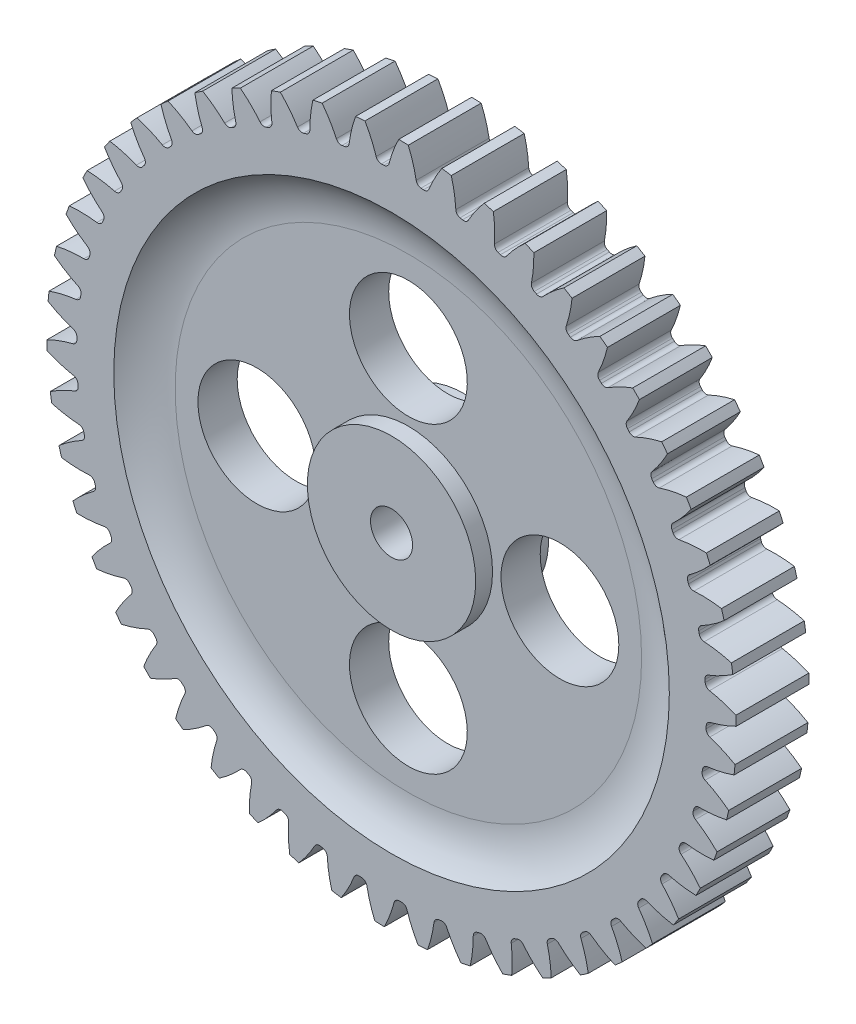
SolidWorks part; units mm, degrees
material "ABS"
ref_plane "Front" through (0, 0, 0) normal (0, 0, 1) x (1, 0, 0)
ref_plane "Top" through (0, 0, 0) normal (0, 1, 0) x (1, 0, 0)
ref_plane "Right" through (0, 0, 0) normal (1, 0, 0) x (0, 0, -1)
sketch "Sketch3" plane through (0, 0, 0) normal (0, 0, 1) x (1, 0, 0)
  circle A0 centre (0, 0) radius 26
  dimension "od" = 52
extrude "gearBody" add sketch "Sketch3" along normal blind 5.5
sketch "Sketch2" plane through (0, 0, 0) normal (0, 0, 1) x (1, 0, 0)
  line L0 (0, 0) -> (21.7041, 8.9901) construction
  line L1 (29.3392, -5.6152) -> (0, 0) construction
  line L2 (0, 0) -> (36.3143, 0) construction
  line L3 (24.9999, -0.0564) -> (24.9435, -1.6792) construction
  line L5 (24.9717, -0.8678) -> (0, 0) construction
  line L7 (0, 0) -> (23.4923, 0) construction
  arc A0 (23.4876, -0.4715) -> (23.4636, -1.1602) centre (0, 0) ccw construction
  arc A1 (25.9973, 0.3721) -> (25.9088, -2.1759) centre (0, 0) ccw construction
  arc A2 (24.9999, -0.0564) -> (24.9435, -1.6792) centre (0, 0) ccw construction
  arc A3 (23.7314, -0.9194) -> (23.738, -0.7303) centre (0, 0) ccw
  arc A4 (29.3392, -5.6152) -> (24.0111, -1.3208) centre (21.0276, -10.4751) ccw
  arc A5 (29.3392, -5.6152) -> (29.6583, 3.5649) centre (0, 0) ccw
  arc A6 (29.6583, 3.5649) -> (24.0448, -0.3492) centre (21.7041, 8.9901) cw
  arc A7 (23.738, -0.7303) -> (24.0448, -0.3492) centre (24.1435, -0.7428) cw
  arc A8 (24.0111, -1.3208) -> (23.7314, -0.9194) centre (24.1368, -0.9351) cw
  point P6 (29.6583, 3.5649)
  point P22 (29.3392, -5.6152)
  dimension "baseDia" = 46.9846
  dimension "od" = 52
  dimension "pd" = 50
  dimension "rd" = 47.4984
  dimension "rFillet" = 0.4057
  dimension "pointX" = 29.6583
  dimension "pointY" = 3.5649
  dimension "CTT" = 1.6228
  dimension "flankCenterAngle" = 22.5
extrude "toothCut" cut sketch "Sketch2" along normal through all
pattern_circular "CirPattern1" count 50 over 360 about axis through (0, 0, 5.5) along (0, 0, -1) of "toothCut"
ref_axis "toothSpace" through (0, 0, 0) along (0.9994, -0.0347, 0)
ref_axis "Axis2" through (25.8763, -2.5328, 0) along (-0.9952, 0.0974, 0)
sketch "boreDia" plane through (0, 0, 0) normal (0, 0, 1) x (1, 0, 0)
  circle A0 centre (0, 0) radius 1.5875
  dimension "boreDia" = 3.175
extrude "bore" cut sketch "boreDia" against normal mid plane 25400
sketch "centerLine" plane through (0, 0, 0) normal (0, 1, 0) x (1, 0, 0)
  line L0 (0, 36.4807) -> (0, -59.6309) construction
ref_plane "CB1plane" through (0, 0, 0) normal (0, 0, -1) x (-1, 0, 0)
ref_plane "CB2plane" through (0, 0, 5.5) normal (0, 0, 1) x (1, 0, 0)
ref_axis "Axis1" through (0, 0, 50) along (0, 0, -1)
sketch "Sketch4" plane through (0, 0, 5.5) normal (0, 0, 1) x (1, 0, 0)
  circle A0 centre (0, 0) radius 20.955
  circle A1 centre (0, 0) radius 6.35
  dimension "D1" = 41.91
  dimension "D2" = 12.7
extrude "Cut-Extrude1" cut sketch "Sketch4" against normal blind 1.27
sketch "Sketch5" plane through (0, 0, 0) normal (0, 0, -1) x (-1, 0, 0)
  circle A0 centre (0, 0) radius 6.35
  circle A1 centre (0, 0) radius 20.955
  dimension "D1" = 12.7
  dimension "D2" = 41.91
extrude "Cut-Extrude2" cut sketch "Sketch5" against normal blind 1.27
fillet "Fillet2" radius 5.08 2 edges at (-20.955, 0, 1.27) (20.955, 0, 4.23)
sketch "Sketch6" plane through (0, 0, 4.23) normal (0, 0, 1) x (1, 0, 0)
  circle A0 centre (11.43, 0) radius 4.445
  dimension "D1" = 8.89
  dimension "D2" = 11.43
extrude "Cut-Extrude3" cut sketch "Sketch6" against normal through all
pattern_circular "CirPattern2" count 4 every 90 about axis through (0, 0, -12700) along (0, 0, 1) of "Cut-Extrude3"
sketch "Sketch7" plane through (0, 0, 5.5) normal (0, 0, 1) x (1, 0, 0)
  circle A0 centre (0, 0) radius 3.175
  dimension "D1" = 6.35
extrude "Cut-Extrude4" [suppressed] cut sketch "Sketch7" against normal up to next
